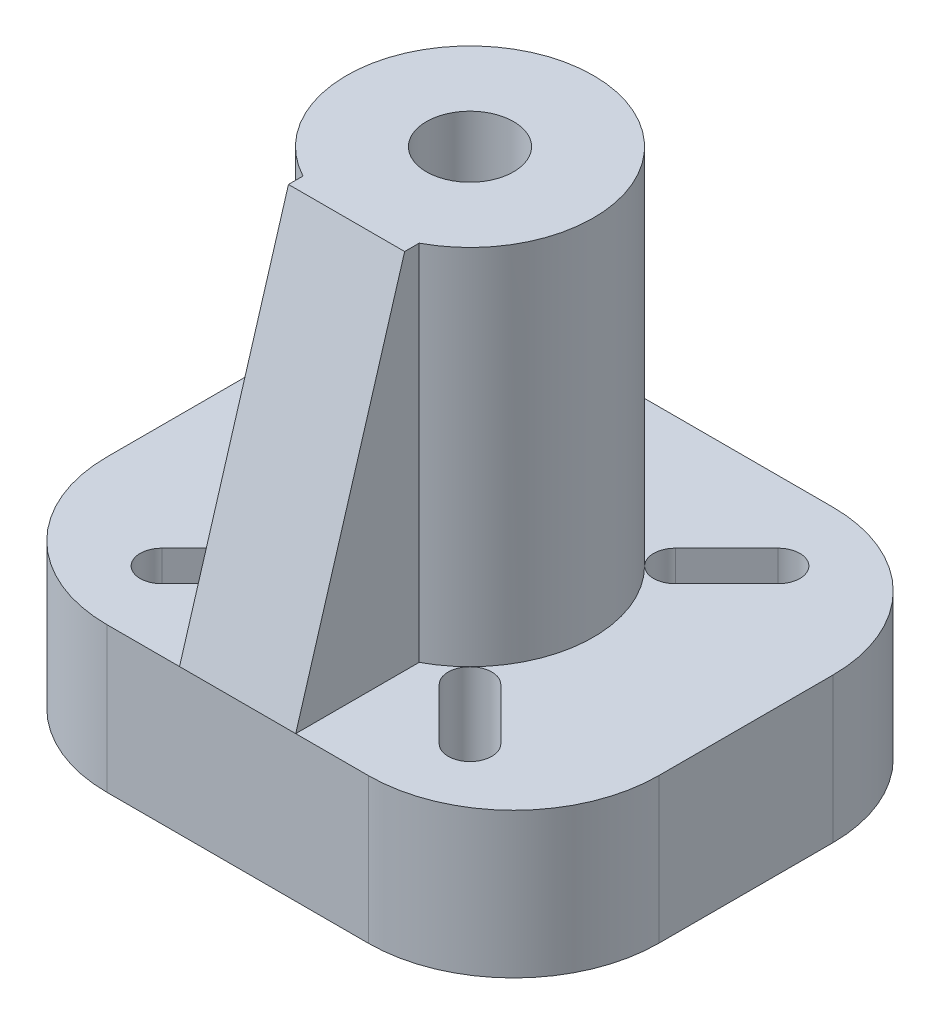
SolidWorks part; units mm, degrees
ref_plane "前视基准面" through (0, 0, 0) normal (0, 0, 1) x (1, 0, 0)
ref_plane "上视基准面" through (0, 0, 0) normal (0, 1, 0) x (1, 0, 0)
ref_plane "右视基准面" through (0, 0, 0) normal (1, 0, 0) x (0, 0, -1)
sketch "草图1" plane through (0, 0, 0) normal (0, 1, 0) x (1, 0, 0)
  line L0 (0, 0) -> (19, 0)
  line L1 (0, 0) -> (-19, 0)
  line L2 (-19, 0) -> (-19, 64)
  line L3 (19, 0) -> (19, 64)
  line L6 (10.6066, 19.9292) -> (10.6066, 16.885)
  line L7 (-7.0711, 47.0711) -> (-10.6066, 50.6066) construction
  line L8 (-8.1317, 46.0104) -> (-11.6673, 49.5459)
  line L9 (-6.0104, 48.1317) -> (-9.5459, 51.6673)
  line L10 (7.0711, 47.0711) -> (10.6066, 50.6066) construction
  line L11 (6.0104, 48.1317) -> (9.5459, 51.6673)
  line L12 (8.1317, 46.0104) -> (11.6673, 49.5459)
  line L13 (7.0711, 32.9289) -> (10.6066, 29.3934) construction
  line L14 (8.1317, 33.9896) -> (11.6673, 30.4541)
  line L15 (6.0104, 31.8683) -> (9.5459, 28.3327)
  line L16 (-7.0711, 32.9289) -> (-10.6066, 29.3934) construction
  line L17 (-6.0104, 31.8683) -> (-9.5459, 28.3327)
  line L18 (-8.1317, 33.9896) -> (-11.6673, 30.4541)
  line L19 (-10.6066, 60.0708) -> (-10.6066, 63.115)
  line L20 (10.6066, 60.0708) -> (10.6066, 63.115)
  line L21 (-10.6066, 19.9292) -> (-10.6066, 16.885)
  arc A0 (-19, 64) -> (19, 64) centre (0, 0) cw
  circle A1 centre (0, 40) radius 5
  arc A2 (-8.1317, 46.0104) -> (-6.0104, 48.1317) centre (-7.0711, 47.0711) ccw
  arc A3 (-9.5459, 51.6673) -> (-11.6673, 49.5459) centre (-10.6066, 50.6066) ccw
  arc A4 (6.0104, 48.1317) -> (8.1317, 46.0104) centre (7.0711, 47.0711) ccw
  arc A5 (11.6673, 49.5459) -> (9.5459, 51.6673) centre (10.6066, 50.6066) ccw
  arc A6 (8.1317, 33.9896) -> (6.0104, 31.8683) centre (7.0711, 32.9289) ccw
  arc A7 (9.5459, 28.3327) -> (11.6673, 30.4541) centre (10.6066, 29.3934) ccw
  arc A8 (-6.0104, 31.8683) -> (-8.1317, 33.9896) centre (-7.0711, 32.9289) ccw
  arc A9 (-11.6673, 30.4541) -> (-9.5459, 28.3327) centre (-10.6066, 29.3934) ccw
  arc A12 (10.6066, 63.115) -> (-10.6066, 63.115) centre (0, 0) ccw
  arc A13 (10.6066, 60.0708) -> (-10.6066, 60.0708) centre (0, 0) ccw
  arc A14 (10.6066, 19.9292) -> (-10.6066, 19.9292) centre (0, 80) cw
  arc A15 (10.6066, 16.885) -> (-10.6066, 16.885) centre (0, 80) cw
  circle A16 centre (-16.1716, 2.8284) radius 1.5
  circle A17 centre (-16.1716, 61.1716) radius 1.5
  circle A18 centre (16.1716, 61.1716) radius 1.5
  circle A19 centre (16.1716, 2.8284) radius 1.5
  point P9 (-8.8388, 48.8388)
  point P19 (8.8388, 48.8388)
  point P26 (8.8388, 31.1612)
  point P33 (-8.8388, 31.1612)
  point P40 (0, 40)
extrude "凸台-拉伸2" add sketch "草图1" along normal blind 3
sketch "草图2" plane through (0, 3, 0) normal (0, 1, 0) x (1, 0, 0)
  line L0 (0, 40) -> (0, 24)
  line L3 (-19, 64) -> (-19, 0) construction
  line L4 (-19, 24) -> (19, 24)
  line L5 (19, 0) -> (19, 64) construction
  line L6 (-19, 24) -> (30.8391, 24)
  line L7 (-19, 24) -> (-19, -5.12)
  line L8 (-19, -5.12) -> (30.8391, -5.12)
  line L9 (30.8391, 24) -> (30.8391, -5.12)
  line M14 (-19, 0) -> (19, 0)
  line M15 (19, 0) -> (19, 64)
  line M17 (-19, 64) -> (-19, 0)
  circle M18 centre (-16.1716, 2.8284) radius 1.5
  arc M28 (-10.6066, 19.9292) -> (10.6066, 19.9292) centre (0, 80) ccw
  line M29 (10.6066, 19.9292) -> (10.6066, 16.885)
  arc M30 (10.6066, 16.885) -> (-10.6066, 16.885) centre (0, 80) cw
  line M31 (-10.6066, 16.885) -> (-10.6066, 19.9292)
  circle M34 centre (16.1716, 2.8284) radius 1.5
extrude "切除-拉伸1" cut sketch "草图2" against normal blind 37 contours L4 M17 M14 M15 M18 M31 M28 M29 M30 M34 region at (0, 3, -11.7105)
sketch "草图3" plane through (0, 0, 0) normal (0, -1, 0) x (1, 0, 0)
  line L0 (-19, -64) -> (-19, -24) construction
  line L1 (19, -64) -> (-19, -64)
  line L2 (19, -64) -> (19, -57.2623)
  line L3 (19, -57.2623) -> (-19, -57.2623)
  line L4 (-19, -64) -> (-19, -57.2623)
extrude "凸台-拉伸3" add sketch "草图3" against normal blind 3
sketch "草图5" plane through (0, 3, 0) normal (0, 1, 0) x (1, 0, 0)
  line L1 (-19, 64) -> (34.6033, 64)
  line L2 (-19, 64) -> (-19, 83.817)
  line L3 (-19, 83.817) -> (34.6033, 83.817)
  line L4 (34.6033, 64) -> (34.6033, 83.817)
extrude "切除-拉伸2" cut sketch "草图5" against normal blind 3
sketch "草图6" plane through (0, 3, 0) normal (0, 1, 0) x (1, 0, 0)
  line L1 (-19, 64) -> (19, 64)
  line L2 (-19, 64) -> (-19, 24)
  line L3 (-19, 24) -> (19, 24)
  line L4 (19, 64) -> (19, 24)
extrude "凸台-拉伸5" add sketch "草图6" along normal blind 7
sketch "草图8" plane through (0, 0, 0) normal (0, -1, 0) x (-1, 0, 0)
  line L1 (-19, 56) -> (19, 56)
  line L2 (-19, 56) -> (-19, 24)
  line L3 (-19, 24) -> (19, 24)
  line L4 (19, 56) -> (19, 24)
  line L5 (-19, 56) -> (19, 24) construction
  line L6 (-19, 24) -> (19, 56) construction
  line L7 (57, 72) -> (-19, 72)
  line L8 (57, 72) -> (57, 56)
  line L9 (57, 56) -> (-19, 56)
  line L10 (-19, 72) -> (-19, 56)
  line L11 (57, 72) -> (-19, 56) construction
  line L12 (57, 56) -> (-19, 72) construction
  point P0 (0, 40)
  point P7 (19, 64)
  line M1 (19, 64) -> (-19, 64)
  line M2 (-19, 64) -> (-19, 24)
  line M4 (19, 24) -> (19, 64)
extrude "切除-拉伸4" cut sketch "草图8" against normal blind 44 contours L1 M2 M4 M1 region at (0, 0, -60)
sketch "草图9" plane through (0, 0, 0) normal (0, -1, 0) x (1, 0, 0)
  circle A0 centre (0, -40) radius 5
extrude "切除-拉伸5" cut sketch "草图9" against normal blind 44
sketch "草图11" plane through (0, 0, 0) normal (0, -1, 0) x (1, 0, 0)
  line L0 (10.6066, -29.3934) -> (7.0711, -32.9289) construction
  line L1 (11.6673, -30.4541) -> (8.1317, -33.9896)
  line L2 (9.5459, -28.3327) -> (6.0104, -31.8683)
  line L3 (10.6066, -50.6066) -> (7.0711, -47.0711) construction
  line L4 (9.5459, -51.6673) -> (6.0104, -48.1317)
  line L5 (11.6673, -49.5459) -> (8.1317, -46.0104)
  line L6 (-10.6066, -50.6066) -> (-7.0711, -47.0711) construction
  line L7 (-11.6673, -49.5459) -> (-8.1317, -46.0104)
  line L8 (-9.5459, -51.6673) -> (-6.0104, -48.1317)
  line L9 (-10.6066, -29.3934) -> (-7.0711, -32.9289) construction
  line L10 (-9.5459, -28.3327) -> (-6.0104, -31.8683)
  line L11 (-11.6673, -30.4541) -> (-8.1317, -33.9896)
  arc A0 (11.6673, -30.4541) -> (9.5459, -28.3327) centre (10.6066, -29.3934) ccw
  arc A1 (6.0104, -31.8683) -> (8.1317, -33.9896) centre (7.0711, -32.9289) ccw
  arc A3 (9.5459, -51.6673) -> (11.6673, -49.5459) centre (10.6066, -50.6066) ccw
  arc A4 (8.1317, -46.0104) -> (6.0104, -48.1317) centre (7.0711, -47.0711) ccw
  arc A5 (-11.6673, -49.5459) -> (-9.5459, -51.6673) centre (-10.6066, -50.6066) ccw
  arc A6 (-6.0104, -48.1317) -> (-8.1317, -46.0104) centre (-7.0711, -47.0711) ccw
  arc A7 (-9.5459, -28.3327) -> (-11.6673, -30.4541) centre (-10.6066, -29.3934) ccw
  arc A8 (-8.1317, -33.9896) -> (-6.0104, -31.8683) centre (-7.0711, -32.9289) ccw
  point P4 (8.8388, -31.1612)
  point P16 (8.8388, -48.8388)
  point P23 (-8.8388, -48.8388)
  point P30 (-8.8388, -31.1612)
  point P35 (0, -40)
  dimension "D1" = 4
extrude "切除-拉伸6" cut sketch "草图11" against normal blind 44
sketch "草图13" plane through (0, 10, 0) normal (0, 1, 0) x (1, 0, 0)
  circle A0 centre (0, 40) radius 8.5
extrude "凸台-拉伸6" add sketch "草图13" along normal blind 25
sketch "草图14" plane through (0, 35, 0) normal (0, 1, 0) x (1, 0, 0)
  circle A0 centre (0, 40) radius 3
extrude "切除-拉伸7" cut sketch "草图14" against normal blind 25
sketch "草图15" plane through (0, 0, 0) normal (1, 0, 0) x (0, 0, -1)
  line L0 (31.5, 35) -> (24, 10)
  line L1 (24, 10) -> (31.5, 10)
  line L2 (31.5, 35) -> (32.9286, 35)
  line L3 (48.5, 35) -> (31.5, 35) construction
  line L4 (32.9286, 35) -> (32.9286, 10)
  line L5 (24, 10) -> (56, 10) construction
  line L6 (32.9286, 10) -> (31.5, 10)
extrude "凸台-拉伸7" add sketch "草图15" along normal mid plane 8
fillet "圆角1" radius 10 4 edges at (19, 5, -24) (-19, 5, -24) (19, 5, -56) (-19, 5, -56)
